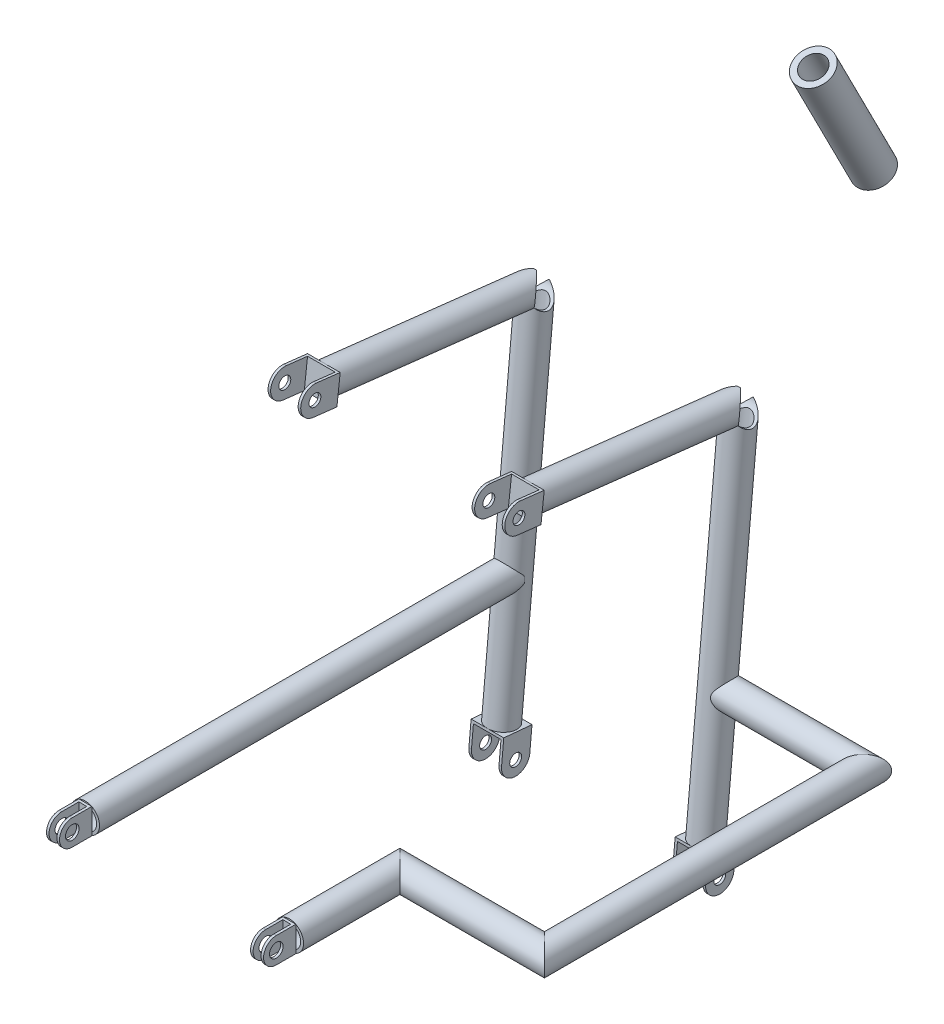
SolidWorks part; units mm, degrees
note: The reader was unsure of these and kept them because the rebuilt part matched: shared geometry of "Croquis20<3>".
ref_plane "Alzado" through (0, 0, 0) normal (0, 0, 1) x (1, 0, 0)
ref_plane "Planta" through (0, 0, 0) normal (0, 1, 0) x (1, 0, 0)
ref_plane "Vista lateral" through (0, 0, 0) normal (1, 0, 0) x (0, 0, -1)
sketch "Croquis1" plane through (0, 0, 0) normal (1, 0, 0) x (0, 0, -1)
  line L0 (-126.8689, 185.2627) -> (151.2953, 153.252) construction
  line L1 (151.2953, 153.252) -> (109.2885, -299.2224) construction
  line L2 (134.4834, -27.837) -> (-285.5166, -27.837) construction
  line L4 (413.203, 226.1853) -> (144.5043, 80.103) construction
  line L5 (385.4898, 280.5756) -> (413.203, 226.1853) construction
  line L6 (385.4898, 280.5756) -> (151.2953, 153.252) construction
  line L7 (-400.8632, -123.7285) -> (-365.4564, -123.7285) construction
  line L8 (-365.4564, -123.7285) -> (-285.5166, -27.837) construction
  dimension "D1" = 280
  dimension "D2" = 266.5677
  dimension "D3" = 305.8415
  dimension "D4" = 420
  dimension "D5" = 150
  dimension "D6" = 452.4743
  dimension "D7" = 91.261
  dimension "D8" = 123.835
  dimension "D9" = 123.835
  dimension "D10" = 95.304
  dimension "D12" = 88.469
  dimension "D13" = 91.531
  dimension "D14" = 181.0889
ref_plane "Plano1" through (120, 0, 0) normal (1, 0, 0) x (0, 0, -1)
sketch "Croquis2" plane through (120, 0, 0) normal (1, 0, 0) x (0, 0, -1)
  line L0 (-380.8632, -108.7285) -> (-380.8632, -138.7285) construction
  line L1 (-400.8632, -108.7285) -> (-380.8632, -108.7285) construction
  line L2 (-380.8632, -138.7285) -> (-400.8632, -138.7285) construction
  line L4 (-100.1236, 198.9951) -> (-103.942, 165.8141) construction
  line L5 (-126.8689, 185.2627) -> (151.2953, 153.252) construction
  line L6 (-124.9597, 201.8532) -> (-100.1236, 198.9951) construction
  line L7 (-128.7781, 168.6722) -> (-103.942, 165.8141) construction
  line L8 (-100.1236, 198.9951) -> (-97.1433, 198.6521) construction
  line L9 (-97.1433, 198.6521) -> (-100.9617, 165.4711) construction
  line L10 (-100.9617, 165.4711) -> (-103.942, 165.8141) construction
  line L11 (-380.8632, -108.7285) -> (-377.8632, -108.7285) construction
  line L12 (-377.8632, -108.7285) -> (-377.8632, -138.7285) construction
  line L13 (-377.8632, -138.7285) -> (-380.8632, -138.7285) construction
  line L14 (94.971, -272.7857) -> (128.228, -275.8732) construction
  line L15 (151.2953, 153.252) -> (109.2885, -299.2224) construction
  line L16 (92.66, -297.6786) -> (94.971, -272.7857) construction
  line L17 (125.917, -300.7661) -> (128.228, -275.8732) construction
  line L18 (94.971, -272.7857) -> (95.2483, -269.7985) construction
  line L19 (95.2483, -269.7985) -> (128.5053, -272.886) construction
  line L20 (128.5053, -272.886) -> (128.228, -275.8732) construction
  line L22 (-400.8632, -123.7285) -> (-365.4564, -123.7285) construction
  circle A0 centre (-400.8632, -123.7285) radius 8 construction
  circle A1 centre (-400.8632, -123.7285) radius 15 construction
  circle A2 centre (-126.8689, 185.2627) radius 16.7 construction
  circle A3 centre (-126.8689, 185.2627) radius 7 construction
  circle A4 centre (109.2885, -299.2224) radius 16.7 construction
  circle A5 centre (109.2885, -299.2224) radius 7 construction
  dimension "D1" = 16
  dimension "D3" = 30
  dimension "D4" = 25
  dimension "D7" = 33.4
  dimension "D8" = 14
  dimension "D11" = 14
  dimension "D2" = 20
  dimension "D5" = 3
  dimension "D6" = 3
  dimension "D9" = 25
  dimension "D10" = 3
ref_plane "Plano2" through (137.7, 0, 0) normal (1, 0, 0) x (0, 0, -1)
sketch "Croquis3" plane through (137.7, 0, 0) normal (1, 0, 0) x (0, 0, -1)
  line L0 (-124.9597, 201.8532) -> (-100.1236, 198.9951) construction
  line L1 (-100.1236, 198.9951) -> (-103.942, 165.8141) construction
  line L2 (-128.7781, 168.6722) -> (-103.942, 165.8141) construction
  line L3 (-124.9597, 201.8532) -> (-100.1236, 198.9951)
  line L4 (-100.1236, 198.9951) -> (-103.942, 165.8141)
  line L5 (-128.7781, 168.6722) -> (-103.942, 165.8141)
  line L6 (125.917, -300.7661) -> (128.228, -275.8732) construction
  line L7 (94.971, -272.7857) -> (128.228, -275.8732) construction
  line L8 (92.66, -297.6786) -> (94.971, -272.7857) construction
  line L9 (125.917, -300.7661) -> (128.228, -275.8732)
  line L10 (94.971, -272.7857) -> (128.228, -275.8732)
  line L11 (92.66, -297.6786) -> (94.971, -272.7857)
  circle A0 centre (-126.8689, 185.2627) radius 7 construction
  circle A1 centre (-126.8689, 185.2627) radius 16.7 construction
  circle A2 centre (-126.8689, 185.2627) radius 7
  arc A3 (-124.9597, 201.8532) -> (-128.7781, 168.6722) centre (-126.8689, 185.2627) ccw
  circle A4 centre (109.2885, -299.2224) radius 16.7 construction
  circle A5 centre (109.2885, -299.2224) radius 7 construction
  arc A6 (92.66, -297.6786) -> (125.917, -300.7661) centre (109.2885, -299.2224) ccw
  circle A7 centre (109.2885, -299.2224) radius 7
extrude "Saliente-Extruir1" add sketch "Croquis3" along normal blind 3
sketch "Croquis4" plane through (140.7, 0, 0) normal (1, 0, 0) x (0, 0, -1)
  line L0 (94.971, -272.7857) -> (95.2483, -269.7985) construction
  line L1 (95.2483, -269.7985) -> (128.5053, -272.886) construction
  line L2 (128.5053, -272.886) -> (128.228, -275.8732) construction
  line L3 (128.228, -275.8732) -> (94.971, -272.7857)
  line L4 (-100.1236, 198.9951) -> (-103.942, 165.8141)
  line L5 (-103.942, 165.8141) -> (-100.9617, 165.4711)
  line L6 (-100.9617, 165.4711) -> (-97.1433, 198.6521)
  line L7 (-97.1433, 198.6521) -> (-100.1236, 198.9951)
  line L9 (94.971, -272.7857) -> (95.2483, -269.7985)
  line L10 (95.2483, -269.7985) -> (128.5053, -272.886)
  line L11 (128.5053, -272.886) -> (128.228, -275.8732)
extrude "Saliente-Extruir2" add sketch "Croquis4" against normal blind 38.4
sketch "Croquis5" plane through (102.3, 0, 0) normal (-1, 0, 0) x (0, 0, 1)
  line L0 (124.9597, 201.8532) -> (100.1236, 198.9951) construction
  line L1 (128.7781, 168.6722) -> (103.942, 165.8141) construction
  line L2 (103.942, 165.8141) -> (100.1236, 198.9951) construction
  line L3 (124.9597, 201.8532) -> (100.1236, 198.9951)
  line L4 (128.7781, 168.6722) -> (103.942, 165.8141)
  line L5 (103.942, 165.8141) -> (100.1236, 198.9951)
  line L6 (-94.971, -272.7857) -> (-92.66, -297.6786) construction
  line L7 (-125.917, -300.7661) -> (-128.228, -275.8732) construction
  line L8 (-128.228, -275.8732) -> (-94.971, -272.7857) construction
  line L9 (-94.971, -272.7857) -> (-92.66, -297.6786)
  line L10 (-125.917, -300.7661) -> (-128.228, -275.8732)
  line L11 (-128.228, -275.8732) -> (-94.971, -272.7857)
  circle A0 centre (126.8689, 185.2627) radius 16.7 construction
  circle A1 centre (126.8689, 185.2627) radius 7 construction
  arc A2 (128.7781, 168.6722) -> (124.9597, 201.8532) centre (126.8689, 185.2627) ccw
  circle A3 centre (126.8689, 185.2627) radius 7
  circle A4 centre (-109.2885, -299.2224) radius 7 construction
  arc A5 (-125.917, -300.7661) -> (-92.66, -297.6786) centre (-109.2885, -299.2224) ccw construction
  circle A6 centre (-109.2885, -299.2224) radius 7
  arc A7 (-125.917, -300.7661) -> (-92.66, -297.6786) centre (-109.2885, -299.2224) ccw
extrude "Saliente-Extruir3" add sketch "Croquis5" against normal blind 3
pattern_linear "MatrizL1" count 2 spacing 240 along (-1, 0, 0) of "Saliente-Extruir1", "Saliente-Extruir2", "Saliente-Extruir3"
ref_plane "Plano3" through (126.3, 0, 0) normal (1, 0, 0) x (0, 0, -1)
sketch "Croquis8" plane through (126.3, 0, 0) normal (1, 0, 0) x (0, 0, -1)
  line L0 (-380.8632, -138.7285) -> (-400.8632, -138.7285) construction
  line L1 (-400.8632, -108.7285) -> (-380.8632, -108.7285) construction
  line L2 (-380.8632, -108.7285) -> (-380.8632, -138.7285) construction
  line L3 (-380.8632, -138.7285) -> (-400.8632, -138.7285)
  line L4 (-400.8632, -108.7285) -> (-380.8632, -108.7285)
  line L5 (-380.8632, -108.7285) -> (-380.8632, -138.7285)
  circle A0 centre (-400.8632, -123.7285) radius 15 construction
  circle A1 centre (-400.8632, -123.7285) radius 8 construction
  arc A2 (-400.8632, -108.7285) -> (-400.8632, -138.7285) centre (-400.8632, -123.7285) ccw
  circle A3 centre (-400.8632, -123.7285) radius 8
extrude "Saliente-Extruir5" add sketch "Croquis8" along normal blind 3 separate body
sketch "Croquis9" plane through (129.3, 0, 0) normal (1, 0, 0) x (0, 0, -1)
  line L0 (-380.8632, -108.7285) -> (-377.8632, -108.7285)
  line L1 (-377.8632, -138.7285) -> (-377.8632, -108.7285)
  line L2 (-377.8632, -138.7285) -> (-380.8632, -138.7285)
  line L3 (-380.8632, -138.7285) -> (-380.8632, -108.7285)
extrude "Saliente-Extruir6" add sketch "Croquis9" against normal blind 15.3
sketch "Croquis10" plane through (114, 0, 0) normal (-1, 0, 0) x (0, 0, 1)
  line L0 (380.8632, -108.7285) -> (400.8632, -108.7285) construction
  line L1 (380.8632, -138.7285) -> (380.8632, -108.7285) construction
  line L2 (400.8632, -138.7285) -> (380.8632, -138.7285) construction
  line L3 (380.8632, -108.7285) -> (400.8632, -108.7285)
  line L4 (380.8632, -138.7285) -> (380.8632, -108.7285)
  line L5 (400.8632, -138.7285) -> (380.8632, -138.7285)
  arc A0 (400.8632, -138.7285) -> (400.8632, -108.7285) centre (400.8632, -123.7285) ccw construction
  circle A1 centre (400.8632, -123.7285) radius 8 construction
  arc A2 (400.8632, -138.7285) -> (400.8632, -108.7285) centre (400.8632, -123.7285) ccw
  circle A3 centre (400.8632, -123.7285) radius 8
extrude "Saliente-Extruir7" add sketch "Croquis10" against normal blind 3
pattern_linear "MatrizL2" count 2 spacing 240 along (-1, 0, 0) of "Saliente-Extruir5", "Saliente-Extruir6", "Saliente-Extruir7"
pattern_linear "MatrizL3" count 2 spacing 240 along (-1, 0, 0) of "Saliente-Extruir6"
ref_plane "Plano4" through (0, -123.7285, 0) normal (0, 1, 0) x (1, 0, 0)
sketch "Croquis11" plane through (0, -123.7285, 0) normal (0, 1, 0) x (1, 0, 0)
  line L0 (121.65, -377.8632) -> (121.65, -247.8632)
  line L1 (291.65, 127.1368) -> (126.3, 127.1368)
  line L2 (114, -377.8632) -> (129.3, -377.8632) construction
  line L3 (291.65, -247.8632) -> (291.65, 127.1368)
  line L4 (126.3, -328.0739) -> (126.3, 328.0739) construction
  line L6 (121.65, -247.8632) -> (291.65, -247.8632)
  dimension "D1" = 130
  dimension "D2" = 170
  dimension "D3" = 375
other "Miembro estructural2" corner treatment miter
ref_plane "Plano6" through (121.65, -123.7285, 377.8632) normal (0, 0, -1) x (-1, 0, 0)
sketch "Sketch1" plane through (121.65, -123.7285, 377.8632) normal (0, 0, -1) x (-1, 0, 0)
  circle A0 centre (0, 0) radius 13.3223
  circle A1 centre (0, 0) radius 16.7005
  circle A2 centre (0, 0) radius 12.7 construction
  point P5 (0, 0)
  dimension "In_dia" = 26.6446
  dimension "Out_dia" = 33.401
  dimension "D1" = 25.4
sketch "Croquis14" plane through (0, -123.7285, 0) normal (0, 1, 0) x (1, 0, 0)
  line L0 (-118.35, -377.8632) -> (-118.35, 122.1368)
  line L1 (-126, -377.8632) -> (-110.7, -377.8632) construction
  line L3 (148.8246, 127.1368) -> (-233.8178, 127.1368) construction
  line L4 (291.65, 127.1368) -> (126.3, 127.1368) construction
  dimension "D1" = 500
other "Miembro estructural3" corner treatment miter
ref_plane "Plano7" through (-118.35, -123.7285, 377.8632) normal (0, 0, -1) x (-1, 0, 0)
sketch "Sketch11" plane through (-118.35, -123.7285, 377.8632) normal (0, 0, -1) x (-1, 0, 0)
  circle A0 centre (0, 0) radius 13.3223
  circle A1 centre (0, 0) radius 16.7005
  circle A2 centre (0, 0) radius 12.7 construction
  point P5 (0, 0)
  dimension "In_dia" = 26.6446
  dimension "Out_dia" = 33.401
  dimension "D1" = 25.4
ref_plane "Plano8" through (0, 280.5756, -385.4898) normal (0, -0.891, -0.454) x (-1, 0, 0)
sketch "Croquis16" plane through (0, 280.5756, -385.4898) normal (0, -0.891, -0.454) x (-1, 0, 0)
  line L0 (0, 0) -> (0, -266.4725) construction
  circle A0 centre (0, 0) radius 21.045
  circle A1 centre (0, 0) radius 13.855
extrude "Saliente-Extruir8" add sketch "Croquis16" along normal blind 100 and the other way blind 56.14 separate body
sketch "Croquis17" plane through (0, -258.7259, 24.0196) normal (0, 0.9957, -0.0924) x (1, 0, 0)
  line L0 (-137.7, 153.1808) -> (-99.3, 119.7808) construction
  line L1 (140.7, 153.1808) -> (102.3, 119.7808) construction
  line L2 (102.3, 153.1808) -> (140.7, 153.1808) construction
  line L3 (140.7, 153.1808) -> (140.7, 119.7808) construction
  line L4 (102.3, 119.7808) -> (140.7, 119.7808) construction
  circle A0 centre (-118.5, 136.4808) radius 16.7
  circle A1 centre (121.5, 136.4808) radius 16.7
extrude "Cortar-Extruir1" cut sketch "Croquis17" along normal blind 316.14
sketch "Croquis18" plane through (0, -258.7259, 24.0196) normal (0, 0.9957, -0.0924) x (1, 0, 0)
  line L0 (-137.7, 153.1808) -> (-99.3, 119.7808) construction
  line L1 (-99.3, 153.1808) -> (-99.3, 119.7808) construction
  line L2 (140.7, 119.7808) -> (102.3, 153.1808) construction
  line L3 (102.3, 119.7808) -> (140.7, 119.7808) construction
  circle A0 centre (-118.5, 136.4808) radius 16.7
  circle A1 centre (121.5, 136.4808) radius 16.7
  circle A2 centre (121.5, 136.4808) radius 13.32
  circle A3 centre (-118.5, 136.4808) radius 13.32
extrude "Saliente-Extruir9" add sketch "Croquis18" along normal blind 426.14 separate body
sketch "Croquis20" plane through (0, 0, 0) normal (1, 0, 0) x (0, 0, -1)
  circle A0 centre (151.2953, 153.252) radius 16.7
extrude "Cortar-Extruir2" cut sketch "Croquis20" against normal mid plane 436.14
sketch "Croquis22" plane through (0, 13.6294, 118.4354) normal (0, -0.1143, -0.9934) x (-1, 0, 0)
  line L0 (-102.3, 152.8438) -> (-140.7, 186.2438) construction
  line L1 (99.3, 186.2438) -> (137.7, 152.8438) construction
  circle A0 centre (-121.5, 169.5438) radius 16.7
  circle A1 centre (-121.5, 169.5438) radius 13.32
  circle A2 centre (118.5, 169.5438) radius 13.32
  circle A3 centre (118.5, 169.5438) radius 16.7
  point P4 (-121.5, 169.5438)
  point P12 (118.5, 169.5438)
extrude "Saliente-Extruir11" add sketch "Croquis22" along normal blind 250 separate body
extrude "Cortar-Extruir4" cut sketch "Croquis20<3>" against normal mid plane 280
sketch "Croquis20<3>" plane through (0, 0, 0) normal (1, 0, 0) x (0, 0, -1) same geometry as "Croquis20"
